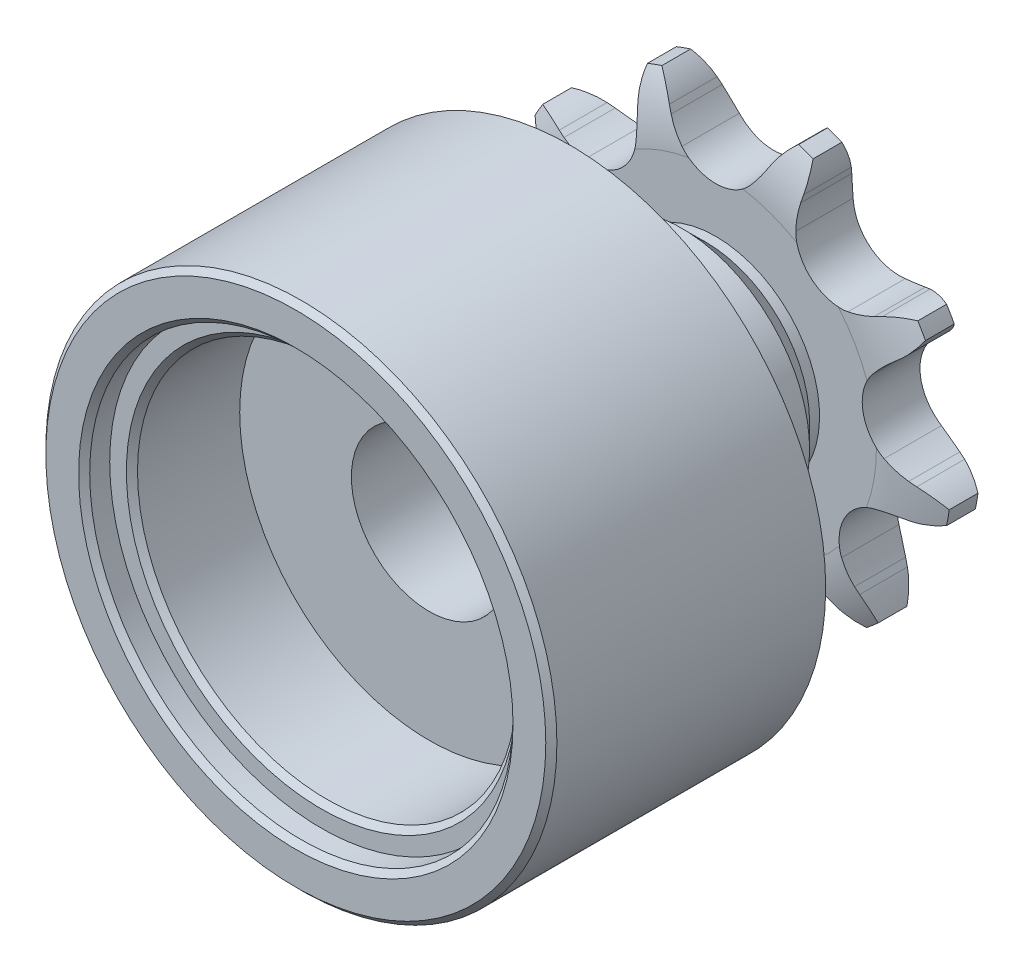
SolidWorks part; units mm, degrees
ref_plane "Front Plane" through (0, 0, 0) normal (0, 0, 1) x (1, 0, 0)
ref_plane "Top Plane" through (0, 0, 0) normal (0, 1, 0) x (1, 0, 0)
ref_plane "Right Plane" through (0, 0, 0) normal (1, 0, 0) x (0, 0, -1)
sketch "Sketch0" plane through (0, 0, 0) normal (0, 0, 1) x (1, 0, 0)
  line L0 (3, -8.2424) -> (0, 0) construction
  line L1 (0, 0) -> (7.5963, -4.3857) construction
  line L2 (0, 0) -> (-3, -8.2424) construction
  line L3 (3, -8.2424) -> (7.5963, -4.3857) construction
  line L4 (3, -8.2424) -> (-3, -8.2424) construction
  line L5 (5.0985, -7.2441) -> (4.8625, -7.0453)
  line L6 (3, -8.2424) -> (0, -9.3343) construction
  line L7 (0.7508, -8.8266) -> (0.8038, -8.5226)
  line L8 (0, -8.2424) -> (0, -10.0424) construction
  line L9 (3.972, -6.4397) -> (1.4813, -11.0591) construction
  line L10 (0, 0) -> (0, -8.2424) construction
  line L11 (4.8625, -7.0453) -> (1.4813, -11.0591) construction
  line L12 (0, -10.0424) -> (0, -10.4354) construction
  line L13 (7.2898, -4.6428) -> (5.0985, -7.2441) construction
  circle A0 centre (0, 0) radius 10.0424 construction
  circle A1 centre (0, 0) radius 8.7714 construction
  arc A2 (-3.6232, -11.4862) -> (10.1587, -6.47) centre (0, 0) ccw
  circle A3 centre (0, 0) radius 10.4354 construction
  circle A4 centre (3, -8.2424) radius 2 construction
  arc A7 (3.972, -6.4397) -> (1.0966, -7.4863) centre (3, -8.2424) ccw
  circle A8 centre (3, -8.2424) radius 2.0481 construction
  arc A9 (5.0985, -7.2441) -> (10.1587, -6.47) centre (7.2898, -4.6428) ccw
  arc A10 (4.8625, -7.0453) -> (3.972, -6.4397) centre (1.4813, -11.0591) ccw
  arc A11 (0.7508, -8.8266) -> (-3.6232, -11.4862) centre (-2.6, -8.2424) cw
  arc A12 (0.8038, -8.5226) -> (1.0966, -7.4863) centre (5.9739, -9.4239) cw
  dimension "D1" = 2.0481
  dimension "R" = 2.0481
sketch "Sketch1" plane through (0, 0, 0) normal (1, 0, 0) x (0, 0, -1)
  line L0 (1.3, 0) -> (-1.3, 0)
  line L1 (-1.3, 0) -> (-1.3, 7.23)
  line L2 (-1.3, 8.7714) -> (0, 8.7714) construction
  line L3 (-0.6, 10.0424) -> (0.6, 10.0424)
  line L5 (1.3, 7.23) -> (1.3, 0)
  line L7 (0, 10.0424) -> (0, 0) construction
  line L8 (-1.3, 7.23) -> (1.3, 7.23) construction
  line L9 (0, 10.0424) -> (0, -10.0424) construction
  line L10 (-1.3, 7.23) -> (-1.3, 10.0424) construction
  line L11 (-1.3, 10.0424) -> (-0.6, 10.0424) construction
  line L12 (0.6, 10.0424) -> (1.3, 10.0424) construction
  line L13 (1.3, 10.0424) -> (1.3, 7.23) construction
  line L14 (0, 0) -> (-6.4008, 0) construction
  line L15 (-1.3, 8.7714) -> (-1.3, 4.6714) construction
  line L22 (1.3, 0) -> (-8.7, 0) construction
  line L24 (-1.3, 0) -> (-1.3, 4.6714) construction
  arc A0 (-0.6, 10.0424) -> (-1.3, 7.23) centre (4.7, 7.23) ccw
  arc A1 (0.6, 10.0424) -> (1.3, 7.23) centre (-4.7, 7.23) cw
  dimension "R" = 6
revolve "Revolve1" add sketch "Sketch1" angle 360 mid plane about L0
extrude "Cut-Extrude1" cut sketch "Sketch0" against normal through all and the other way through all
pattern_circular "CirPattern1" count 9 over 360 about axis through (0, 0, -1.3) along (0, 0, -1) of "Cut-Extrude1"
sketch "Sketch2" plane through (0, 0, 0) normal (0, 0, 1) x (1, 0, 0)
  circle A0 centre (0, 0) radius 2.5 construction
  circle A1 centre (0, 0) radius 5.75
  circle A2 centre (0, 0) radius 9.95 construction
  dimension "Bore" = 5
  dimension "Hub Dia." = 11.5
  dimension "OD" = 19.9
extrude "Boss-Extrude1" add sketch "Sketch2" along normal up to vertex (8.7 mm away) from surface up to point (0, 0, 8.7) starting at face at (0, 0, 1.3)
sketch "Sketch3" plane through (0, 0, 0) normal (0, 0, 1) x (1, 0, 0)
  circle A0 centre (0, 0) radius 2.5 construction
  circle A1 centre (0, 0) radius 2.5
extrude "Cut-Extrude2" cut sketch "Sketch3" along normal through all and the other way through all
sketch "Sketch4" plane through (0, 0, 0) normal (1, 0, 0) x (0, 0, -1)
  line L0 (-8.7, 5.75) -> (-8.7, 5.25)
  line L1 (-1.3, 10.0424) -> (-3.25, 10.0424)
  line L2 (-1.3, 10.0424) -> (-1.3, 4.6714)
  line L3 (-1.3, 4.6714) -> (-3.25, 4.6714)
  line L4 (-3.25, 10.0424) -> (-3.25, 4.6714)
  line L9 (-8.7, 5.25) -> (-8.2, 5.75)
  line L10 (-8.2, 5.75) -> (-8.7, 5.75)
  dimension "C" = 0.5
  dimension "D3" = 1.95
revolve "Cut-Revolve1" cut sketch "Sketch4" angle 360 mid plane about L22
sketch "Sketch5" plane through (0, 0, 0) normal (0, 0, 1) x (1, 0, 0)
  circle A0 centre (0, 0) radius 9.95 construction
  circle A1 centre (0, 0) radius 9.95
extrude "Cut-Extrude3" cut sketch "Sketch5" against normal through all and the other way through all flip side to cut
ref_plane "Plane1" through (0, 0, 8.2) normal (0, 0, 1) x (1, 0, 0)
sketch "Sketch6" plane through (0, 0, 8.2) normal (0, 0, 1) x (1, 0, 0)
  circle A0 centre (0, 0) radius 11.5
  dimension "D1" = 23
extrude "Boss-Extrude2" add sketch "Sketch6" along normal blind 12
sketch "Sketch7" plane through (0, 0, 0) normal (0, 0, 1) x (1, 0, 0)
  circle A0 centre (0, 0) radius 3.5
  dimension "D1" = 7
extrude "Cut-Extrude4" cut sketch "Sketch7" against normal through all both and the other way through all
sketch "Sketch8" plane through (0, 0, 20.2) normal (0, 0, 1) x (1, 0, 0)
  circle A0 centre (0, 0) radius 8.525
  dimension "D1" = 17.05
extrude "Cut-Extrude5" cut sketch "Sketch8" against normal blind 6
sketch "Sketch9" plane through (0, 0, 20.2) normal (0, 0, 1) x (1, 0, 0)
  circle A0 centre (0, 0) radius 9.525
  dimension "D1" = 19.05
extrude "Cut-Extrude6" cut sketch "Sketch9" against normal blind 1.15
chamfer "Chamfer1" distance 1.5 distance2 1.5 1 edges at (0, 4.6714, 3.25)
chamfer "Chamfer2" distance 3 distance2 6.5 1 edges at (5.75, 0, 8.2) first distance on face at (0, -5.75, 2.8286)
chamfer "Chamfer3" distance 0.25 angle 45 3 edges at (11.5, 0, 20.2) (9.525, 0, 20.2) (8.525, 0, 19.05)
equation "\"360/N@Sketch0\" = 360/\"Teeth@CirPattern1\""
equation "\"Ds@Sketch0\" = 1.005 * \"Dr@Sketch0\" + ( 0.003 * 25.4 ) "
equation "\"R@Sketch0\" = 1/2 * \"Ds@Sketch0\""
equation "\"A@Sketch0\" = 35 +  ( 60 / \"Teeth@CirPattern1\" ) "
equation "\"B@Sketch0\" = 18 -  ( 56 / \"Teeth@CirPattern1\" )"
equation "\"ac@Sketch0\" = 0.8 * \"Dr@Sketch0\""
equation "\"ab@Sketch0\" = 1.4 * \"Dr@Sketch0\""
equation "\"J@Sketch0\" = 0.3 * \"Pitch@Sketch0\""
equation "\"D3@Sketch4\" = \"t@Sketch1\" * 3 / 4"
